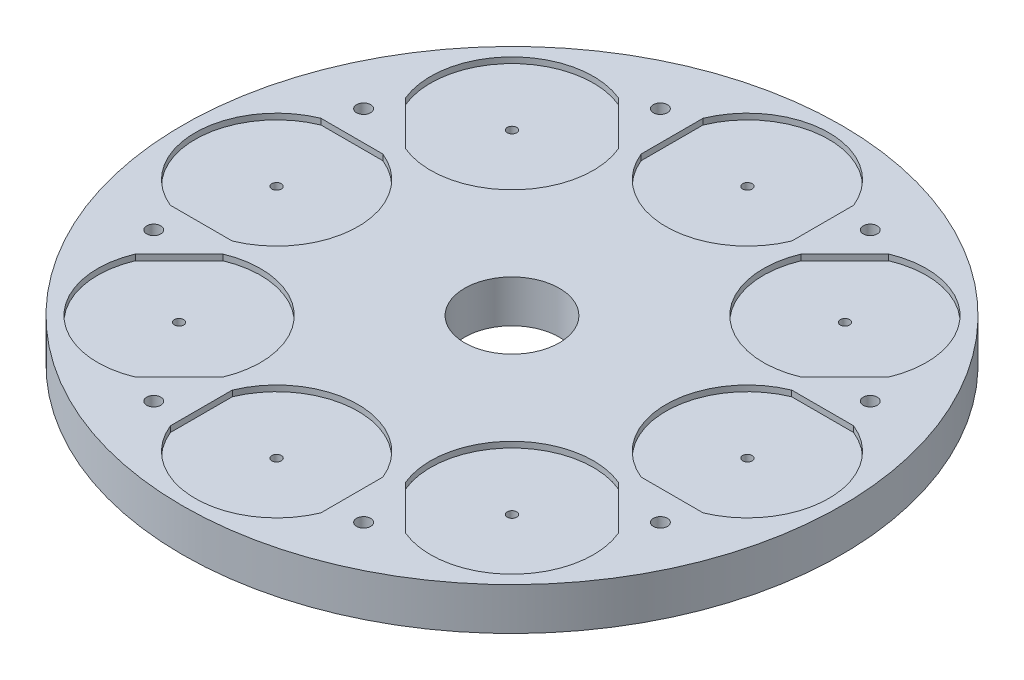
SolidWorks part; units mm, degrees
ref_plane "Front Plane" through (0, 0, 0) normal (0, 0, 1) x (1, 0, 0)
ref_plane "Top Plane" through (0, 0, 0) normal (0, 1, 0) x (1, 0, 0)
ref_plane "Right Plane" through (0, 0, 0) normal (1, 0, 0) x (0, 0, -1)
sketch "Sketch1" plane through (0, 0, 0) normal (0, 1, 0) x (1, 0, 0)
  line L0 (70, 0) -> (50, 0) construction
  circle A0 centre (0, 0) radius 70
  circle A1 centre (50, 0) radius 12
  circle A2 centre (35.3553, -35.3553) radius 12
  circle A3 centre (0, -50) radius 12
  circle A4 centre (-35.3553, -35.3553) radius 12
  circle A5 centre (-50, 0) radius 12
  circle A6 centre (-35.3553, 35.3553) radius 12
  circle A7 centre (0, 50) radius 12
  circle A8 centre (35.3553, 35.3553) radius 12
  point P23 (0, 0)
  dimension "D1" = 140
  dimension "D3" = 24
  dimension "D2" = 20
  dimension "D4" = 8
extrude "Boss-Extrude1" add sketch "Sketch1" along normal blind 25
sketch "Sketch2" plane through (0, 25, 0) normal (0, 1, 0) x (1, 0, 0)
  line L0 (50, 0) -> (50, 16) construction
  line L1 (50, 16) -> (43.4205, 16)
  line L2 (50, 16) -> (56.5795, 16)
  line L3 (32.7, 0) -> (67.3, 0) construction
  line L4 (50, -16) -> (56.5795, -16)
  line L5 (50, -16) -> (43.4205, -16)
  line L6 (46.669, -24.0416) -> (42.0166, -19.3892)
  line L7 (24.0416, -46.669) -> (19.3892, -42.0166)
  line L8 (24.0416, -46.669) -> (28.694, -51.3215)
  line L9 (46.669, -24.0416) -> (51.3215, -28.694)
  line L10 (16, -50) -> (16, -43.4205)
  line L11 (-16, -50) -> (-16, -43.4205)
  line L12 (-16, -50) -> (-16, -56.5795)
  line L13 (16, -50) -> (16, -56.5795)
  line L14 (-24.0416, -46.669) -> (-19.3892, -42.0166)
  line L15 (-46.669, -24.0416) -> (-42.0166, -19.3892)
  line L16 (-46.669, -24.0416) -> (-51.3215, -28.694)
  line L17 (-24.0416, -46.669) -> (-28.694, -51.3215)
  line L18 (-50, -16) -> (-43.4205, -16)
  line L19 (-50, 16) -> (-43.4205, 16)
  line L20 (-50, 16) -> (-56.5795, 16)
  line L21 (-50, -16) -> (-56.5795, -16)
  line L22 (-46.669, 24.0416) -> (-42.0166, 19.3892)
  line L23 (-24.0416, 46.669) -> (-19.3892, 42.0166)
  line L24 (-24.0416, 46.669) -> (-28.694, 51.3215)
  line L25 (-46.669, 24.0416) -> (-51.3215, 28.694)
  line L26 (-16, 50) -> (-16, 43.4205)
  line L27 (16, 50) -> (16, 43.4205)
  line L28 (16, 50) -> (16, 56.5795)
  line L29 (-16, 50) -> (-16, 56.5795)
  line L30 (24.0416, 46.669) -> (19.3892, 42.0166)
  line L31 (46.669, 24.0416) -> (42.0166, 19.3892)
  line L32 (46.669, 24.0416) -> (51.3215, 28.694)
  line L33 (24.0416, 46.669) -> (28.694, 51.3215)
  arc A0 (43.4205, 16) -> (43.4205, -16) centre (50, 0) ccw
  arc A1 (56.5795, -16) -> (56.5795, 16) centre (50, 0) ccw
  arc A2 (42.0166, -19.3892) -> (19.3892, -42.0166) centre (35.3553, -35.3553) ccw
  arc A3 (28.694, -51.3215) -> (51.3215, -28.694) centre (35.3553, -35.3553) ccw
  arc A4 (16, -43.4205) -> (-16, -43.4205) centre (0, -50) ccw
  arc A5 (-16, -56.5795) -> (16, -56.5795) centre (0, -50) ccw
  arc A6 (-19.3892, -42.0166) -> (-42.0166, -19.3892) centre (-35.3553, -35.3553) ccw
  arc A7 (-51.3215, -28.694) -> (-28.694, -51.3215) centre (-35.3553, -35.3553) ccw
  arc A8 (-43.4205, -16) -> (-43.4205, 16) centre (-50, 0) ccw
  arc A9 (-56.5795, 16) -> (-56.5795, -16) centre (-50, 0) ccw
  arc A10 (-42.0166, 19.3892) -> (-19.3892, 42.0166) centre (-35.3553, 35.3553) ccw
  arc A11 (-28.694, 51.3215) -> (-51.3215, 28.694) centre (-35.3553, 35.3553) ccw
  arc A12 (-16, 43.4205) -> (16, 43.4205) centre (0, 50) ccw
  arc A13 (16, 56.5795) -> (-16, 56.5795) centre (0, 50) ccw
  arc A14 (19.3892, 42.0166) -> (42.0166, 19.3892) centre (35.3553, 35.3553) ccw
  arc A15 (51.3215, 28.694) -> (28.694, 51.3215) centre (35.3553, 35.3553) ccw
  point P61 (0, 0)
  dimension "D1" = 34.6
  dimension "D2" = 16
  dimension "D3" = 8
extrude "Cut-Extrude1" cut sketch "Sketch2" against normal blind 10
ref_plane "Plane1" through (0, 10, 0) normal (0, 1, 0) x (1, 0, 0)
split "Split1" trim tools "Plane1" bodies to split 102 resulting bodies 103 104
delete or keep bodies "Body-Delete/Keep 1" type delete bodies bodies 104
sketch "Sketch3" plane through (0, 10, 0) normal (0, -1, 0) x (1, 0, 0)
  circle A0 centre (0, 0) radius 20
  dimension "D1" = 40
extrude "Cut-Extrude2" cut sketch "Sketch3" against normal blind 7.5
sketch "Sketch4" plane through (0, 25, 0) normal (0, 1, 0) x (1, 0, 0)
  circle A0 centre (0, 0) radius 70
extrude "Cut-Extrude3" cut sketch "Sketch4" against normal blind 6
sketch "Sketch5" plane through (0, 19, 0) normal (0, 1, 0) x (1, 0, 0)
  line L0 (-70, 0) -> (70, 0) construction
  line L1 (0, 4) -> (0, -4) construction
  circle A1 centre (0, 0) radius 70 construction
  circle A2 centre (0, -4) radius 1.5
  circle A3 centre (0, 4) radius 1.5
  circle A4 centre (-4, 0) radius 1.5
  circle A5 centre (4, 0) radius 1.5
  point P11 (0, 0)
  dimension "D1" = 3
  dimension "D3" = 4
  dimension "D2" = 8
extrude "Cut-Extrude4" cut sketch "Sketch5" against normal through all
sketch "Sketch6" plane through (0, 19, 0) normal (0, 1, 0) x (1, 0, 0)
  line L0 (-16, 43.4205) -> (-19.3892, 42.0166) construction
  line L1 (-17.6946, 42.7186) -> (-26.7878, 64.6716) construction
  circle A0 centre (0, 0) radius 70 construction
  circle A1 centre (-22.2868, 53.8051) radius 1.5
  circle A2 centre (22.2868, 53.8051) radius 1.5
  circle A3 centre (53.8051, 22.2868) radius 1.5
  circle A4 centre (53.8051, -22.2868) radius 1.5
  circle A5 centre (22.2868, -53.8051) radius 1.5
  circle A6 centre (-22.2868, -53.8051) radius 1.5
  circle A7 centre (-53.8051, -22.2868) radius 1.5
  circle A8 centre (-53.8051, 22.2868) radius 1.5
  point P19 (0, 0)
  dimension "D1" = 12
  dimension "D3" = 3
  dimension "D2" = 21.953
  dimension "D4" = 8
sketch "Sketch7" plane through (0, 17.5, 0) normal (0, -1, 0) x (1, 0, 0)
  circle A0 centre (0, 0) radius 20
extrude "Boss-Extrude2" add sketch "Sketch7" along normal up to surface and the other way up to surface up to face at (0, 10, -20) other way up to face at (0, 19, 5.5)
sketch "Sketch9" plane through (0, 10, 0) normal (0, -1, 0) x (1, 0, 0)
  circle A0 centre (0, 50) radius 12
  circle A1 centre (0, 50) radius 2.4904
  circle A2 centre (35.3553, 35.3553) radius 2.4904
  circle A3 centre (35.3553, 35.3553) radius 12
  circle A4 centre (50, 0) radius 2.4904
  circle A5 centre (50, 0) radius 12
  circle A6 centre (35.3553, -35.3553) radius 2.4904
  circle A7 centre (35.3553, -35.3553) radius 12
  circle A8 centre (0, -50) radius 2.4904
  circle A9 centre (0, -50) radius 12
  circle A10 centre (-35.3553, -35.3553) radius 2.4904
  circle A11 centre (-35.3553, -35.3553) radius 12
  circle A12 centre (-50, 0) radius 2.4904
  circle A13 centre (-50, 0) radius 12
  circle A14 centre (-35.3553, 35.3553) radius 2.4904
  circle A15 centre (-35.3553, 35.3553) radius 12
  point P28 (0, 0)
  dimension "D1" = 8
extrude "Boss-Extrude3" add sketch "Sketch9" against normal up to surface (5 mm away) up to face at (50, 15, 12)
extrude "Cut-Extrude5" cut sketch "Sketch6" against normal through all
sketch "Sketch10" plane through (0, 15, 0) normal (0, 1, 0) x (1, 0, 0)
  line L0 (16, -56.5795) -> (16, -43.4205)
  line L1 (-16, -56.5795) -> (-16, -43.4205)
  line L16 (-28.694, -51.3215) -> (-19.3892, -42.0166)
  line L17 (-51.3215, -28.694) -> (-42.0166, -19.3892)
  line L18 (-56.5795, -16) -> (-43.4205, -16)
  line L19 (-56.5795, 16) -> (-43.4205, 16)
  line L20 (-51.3215, 28.694) -> (-42.0166, 19.3892)
  line L21 (-28.694, 51.3215) -> (-19.3892, 42.0166)
  line L22 (-16, 56.5795) -> (-16, 43.4205)
  line L23 (16, 56.5795) -> (16, 43.4205)
  line L24 (28.694, 51.3215) -> (19.3892, 42.0166)
  line L25 (51.3215, 28.694) -> (42.0166, 19.3892)
  line L26 (56.5795, 16) -> (43.4205, 16)
  line L27 (56.5795, -16) -> (43.4205, -16)
  line L28 (51.3215, -28.694) -> (42.0166, -19.3892)
  line L29 (28.694, -51.3215) -> (19.3892, -42.0166)
  arc A0 (16, -43.4205) -> (-16, -43.4205) centre (0, -50) ccw
  arc A1 (-16, -56.5795) -> (16, -56.5795) centre (0, -50) ccw
  circle A16 centre (0, -50) radius 2.4904
  arc A17 (-19.3892, -42.0166) -> (-42.0166, -19.3892) centre (-35.3553, -35.3553) ccw
  arc A18 (-51.3215, -28.694) -> (-28.694, -51.3215) centre (-35.3553, -35.3553) ccw
  circle A19 centre (-35.3553, -35.3553) radius 2.4904
  arc A20 (-43.4205, -16) -> (-43.4205, 16) centre (-50, 0) ccw
  arc A21 (-56.5795, 16) -> (-56.5795, -16) centre (-50, 0) ccw
  circle A22 centre (-50, 0) radius 2.4904
  arc A23 (-42.0166, 19.3892) -> (-19.3892, 42.0166) centre (-35.3553, 35.3553) ccw
  arc A24 (-28.694, 51.3215) -> (-51.3215, 28.694) centre (-35.3553, 35.3553) ccw
  circle A25 centre (-35.3553, 35.3553) radius 2.4904
  arc A26 (-16, 43.4205) -> (16, 43.4205) centre (0, 50) ccw
  arc A27 (16, 56.5795) -> (-16, 56.5795) centre (0, 50) ccw
  circle A28 centre (0, 50) radius 2.4904
  arc A29 (19.3892, 42.0166) -> (42.0166, 19.3892) centre (35.3553, 35.3553) ccw
  arc A30 (51.3215, 28.694) -> (28.694, 51.3215) centre (35.3553, 35.3553) ccw
  circle A31 centre (35.3553, 35.3553) radius 2.4904
  arc A32 (43.4205, 16) -> (43.4205, -16) centre (50, 0) ccw
  arc A33 (56.5795, -16) -> (56.5795, 16) centre (50, 0) ccw
  circle A34 centre (50, 0) radius 2.4904
  arc A35 (42.0166, -19.3892) -> (19.3892, -42.0166) centre (35.3553, -35.3553) ccw
  arc A36 (28.694, -51.3215) -> (51.3215, -28.694) centre (35.3553, -35.3553) ccw
  circle A37 centre (35.3553, -35.3553) radius 2.4904
  point P49 (0, 0)
  point P58 (0, 0)
  dimension "D1" = 8
extrude "Boss-Extrude5" add sketch "Sketch10" along normal blind 2.76
sketch "Sketch11" plane through (0, 19, 0) normal (0, 1, 0) x (1, 0, 0)
  circle A0 centre (0, 0) radius 10.0532
extrude "Cut-Extrude7" cut sketch "Sketch11" against normal through all
sketch "Sketch12" plane through (0, 10, 0) normal (0, -1, 0) x (1, 0, 0)
  circle A1 centre (-35.3553, 35.3553) radius 2.4904
  circle A2 centre (-35.3553, 35.3553) radius 1.75
  circle A3 centre (0, 50) radius 2.4904
  circle A4 centre (0, 50) radius 1.75
  circle A5 centre (35.3553, 35.3553) radius 2.4904
  circle A6 centre (35.3553, 35.3553) radius 1.75
  circle A7 centre (50, 0) radius 2.4904
  circle A8 centre (50, 0) radius 1.75
  circle A9 centre (35.3553, -35.3553) radius 2.4904
  circle A10 centre (35.3553, -35.3553) radius 1.75
  circle A11 centre (0, -50) radius 2.4904
  circle A12 centre (0, -50) radius 1.75
  circle A13 centre (-35.3553, -35.3553) radius 2.4904
  circle A14 centre (-35.3553, -35.3553) radius 1.75
  circle A15 centre (-50, 0) radius 2.4904
  circle A16 centre (-50, 0) radius 1.75
  point P28 (0, 0)
  dimension "D1" = 3.5
  dimension "D2" = 8
extrude "Boss-Extrude6" add sketch "Sketch12" against normal up to surface (7.76 mm away) up to face at (0, 17.76, 50)
sketch "Sketch13" plane through (0, 10, 0) normal (0, -1, 0) x (1, 0, 0)
  circle A0 centre (-35.3553, 35.3553) radius 1.75
  circle A1 centre (-35.3553, 35.3553) radius 1
  circle A2 centre (0, 50) radius 1.75
  circle A3 centre (0, 50) radius 1
  circle A4 centre (35.3553, 35.3553) radius 1.75
  circle A5 centre (35.3553, 35.3553) radius 1
  circle A6 centre (50, 0) radius 1.75
  circle A7 centre (50, 0) radius 1
  circle A8 centre (35.3553, -35.3553) radius 1.75
  circle A9 centre (35.3553, -35.3553) radius 1
  circle A10 centre (0, -50) radius 1.75
  circle A11 centre (0, -50) radius 1
  circle A12 centre (-35.3553, -35.3553) radius 1.75
  circle A13 centre (-35.3553, -35.3553) radius 1
  circle A14 centre (-50, 0) radius 1.75
  circle A15 centre (-50, 0) radius 1
  point P28 (0, 0)
  dimension "D1" = 2
  dimension "D2" = 8
extrude "Boss-Extrude7" add sketch "Sketch13" against normal up to surface (7.76 mm away) and the other way blind 5 up to face at (35.3553, 17.76, 35.3553)
